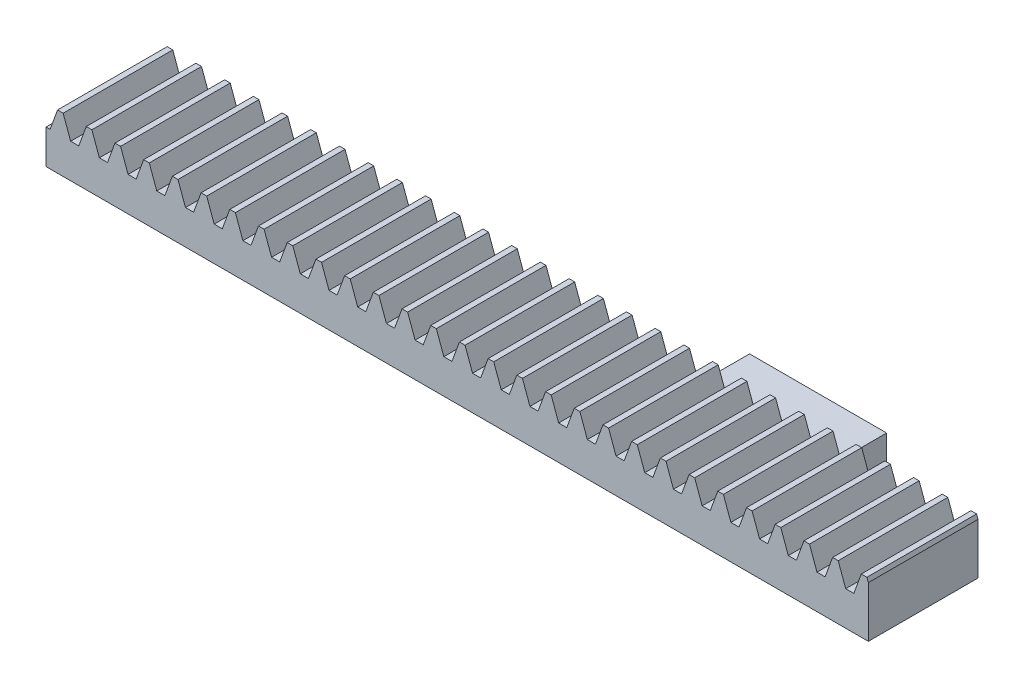
SolidWorks part; units mm, degrees
extrude "Blank" add sketch "BlankSke" against normal blind 12
sketch "BlankSke" plane through (0, 0, 0) normal (0, 0, 1) x (1, 0, 0)
  line L1 (0, 0) -> (90, 0)
  line L2 (0, 0) -> (0, 6)
  line L3 (0, 6) -> (90, 6)
  line L4 (90, 0) -> (90, 6)
  dimension "Length" = 90
ref_plane "Plane1" through (0, 0, 0) normal (0, 0, 1) x (1, 0, 0)
ref_plane "Plane2" through (0, 0, 0) normal (0, 1, 0) x (1, 0, 0)
ref_plane "Plane3" through (0, 0, 0) normal (1, 0, 0) x (0, 0, -1)
sketch "HoldingSke" plane through (0, 0, 0) normal (0, 1, 0) x (1, 0, 0)
  line L0 (0, 0) -> (0.1392, 0.9903)
  line L1 (-15, 0) -> (100, 0) construction
  line L2 (0, 0) -> (-2.1039, 2.3779)
  line L3 (0, 0) -> (-11.863, 4.5341)
  line L4 (0, 0) -> (7.479, 4.318)
  line L5 (0, 0) -> (-23.7986, -8.8762)
  line L6 (0, 0) -> (-10.5278, -7.1032)
  line L9 (-71.009, 38.7566) -> (13.5634, 69.5384)
  line L10 (-76.2, 3.3779) -> (-71.2, 3.3779)
  line L11 (0, 0) -> (-12, 0)
  line L12 (-76.2, 101.6) -> (-76.162, 101.6)
  line L13 (24.9733, 27.94) -> (52.9518, 28.4284)
  line L14 (24.9733, 27.94) -> (24.9743, 27.94)
  line L15 (24.9733, 27.94) -> (100.4006, 29.5858)
  circle A0 centre (0, 0) radius 19.05
  circle A1 centre (0, 0) radius 2.5
  circle A2 centre (0, 0) radius 12.7
  dimension "Num_teeth" = 30
  dimension "Width" = 12
  dimension "Length" = 90
  dimension "Pitch_height" = 5
sketch "TooCutSkeIll" plane through (0, 0, 0) normal (0, 0, 1) x (1, 0, 0)
  line L0 (-1.2538, 5.9737) -> (-0.5045, 3.9152)
  line L1 (-0.2687, 3.75) -> (0.2687, 3.75)
  line L2 (0.5045, 3.9152) -> (1.2538, 5.9737)
  line L3 (90, 6) -> (0, 6) construction
  line L4 (0, 0) -> (0, 64.897) construction
  line L5 (-13.208, 5) -> (12.954, 5) construction
  line L6 (0, 0) -> (90, 0) construction
  line L7 (0.8994, 5) -> (0.8994, 48.7463) construction
  line L8 (-0.8994, 5) -> (-0.8994, 48.7463) construction
  line L9 (1.2914, 6) -> (1.2914, 6.0254)
  line L10 (-1.2914, 6) -> (-1.2914, 6.0254)
  line L11 (-1.2914, 6.0254) -> (1.2914, 6.0254)
  arc A0 (0.2687, 3.75) -> (0.5045, 3.9152) centre (0.2687, 4.001) ccw
  arc A1 (-0.5045, 3.9152) -> (-0.2687, 3.75) centre (-0.2687, 4.001) ccw
  arc A2 (1.2914, 6) -> (1.2538, 5.9737) centre (1.2914, 5.96) ccw
  arc A3 (-1.2538, 5.9737) -> (-1.2914, 6) centre (-1.2914, 5.96) ccw
  dimension "Addendum_plus" = 1.0254
  dimension "Pitch_height" = 5
  dimension "Pressure_angle" = 20
  dimension "Gap_width" = 1.7988
  dimension "Dedendum" = 1.25
extrude "ToothCutIll" [suppressed] cut sketch "TooCutSkeIll" against normal through all
sketch "TooCutSkeSim" plane through (0, 0, 0) normal (0, 0, 1) x (1, 0, 0)
  line L0 (0.4444, 3.75) -> (-0.4444, 3.75)
  line L1 (1.2726, 6.0254) -> (0.4444, 3.75)
  line L2 (0, 17.4625) -> (0, 53.467) construction
  line L3 (1.2726, 6.0254) -> (-1.2726, 6.0254)
  line L6 (-1.2726, 6.0254) -> (-0.4444, 3.75)
  line L9 (-0.8994, 5) -> (0.8994, 5) construction
  line L10 (0, 0) -> (90, 0) construction
  line L11 (0.8994, 5) -> (0.8994, 53.467) construction
  line L12 (-0.8994, 5) -> (-0.8994, 53.467) construction
  dimension "Addendum_plus" = 1.0254
  dimension "Pitch_height" = 5
  dimension "Pressure_angle" = 20
  dimension "Gap_width" = 1.7988
  dimension "Dedendum" = 1.25
extrude "ToothCutSim" cut sketch "TooCutSkeSim" against normal through all
pattern_linear "TeethCuts" count 30 spacing 3.1416 along (1, 0, 0) of "ToothCutIll", "ToothCutSim"
sketch "Sketch1" plane through (0, 0, -12) normal (0, 0, -1) x (-1, 0, 0)
  line L0 (0, 0) -> (-90, 0) construction
  line L1 (-75, 0) -> (-60, 0)
  line L2 (-75, 0) -> (-75, 3.75)
  line L3 (-75, 3.75) -> (-60, 3.75)
  line L4 (-60, 0) -> (-60, 3.75)
  line L5 (0, 3.75) -> (0, 0) construction
  dimension "D1" = 60
  dimension "D2" = 15
extrude "Boss-Extrude1" add sketch "Sketch1" along normal blind 5
equation "' \"Module@HoldingSke\" = 6.35"
equation "' \"Num_teeth@HoldingSke\" = 12"
equation "' \"Ap@HoldingSke\" =  20"
equation "' \"Ap@HoldingSke\" = 20"
equation "' \"Width@HoldingSke\" = 0.25 * 25.4"
equation "' \"Show_teeth@HoldingSke\" = 500"
equation "' \"Backlash@HoldingSke\" = 0.009 * 25.4"
equation "' \"Addendum_fac@HoldingSke\" = 1.0"
equation "' \"Dedendum_fac@HoldingSke\" = 1.25"
equation "' \"Dedendum_add@HoldingSke\" = 0.00005 * 25.4"
equation "' \"Clearance_fac@HoldingSke\" = 0.25"
equation "' \"Pitch_height@HoldingSke\" = 1 * 25.4"
equation "' \"Length@HoldingSke\" = 4.71 * 25.4"
equation "\"Pitch@HoldingSke\" = 1 / \"Module@HoldingSke\""
equation "\"MPH@HoldingSke\" = \"Dedendum_fac@HoldingSke\" / \"Pitch@HoldingSke\" + 2 * \"Dedendum_add@HoldingSke\" + 0.002 * 25.4"
equation "\"MPH@HoldingSke\" = ((sgn( \"MPH@HoldingSke\" - \"Pitch_height@HoldingSke\")+1)*( \"MPH@HoldingSke\" - \"Pitch_height@HoldingSke\"))/2 + \"Pitch_height@HoldingSke\""
equation "\"Blank_height@BlankSke\" = \"Pitch_height@HoldingSke\" + \"Addendum_fac@HoldingSke\"  / \"Pitch@HoldingSke\" "
equation "\"Length@BlankSke\" =  \"Length@HoldingSke\""
equation "\"Face_width@Blank\" = \"Width@HoldingSke\""
equation "\"Pressure_angle@TooCutSkeIll\" = \"Ap@HoldingSke\""
equation "\"Addendum_plus@TooCutSkeIll\" =  \"Addendum_fac@HoldingSke\"  / \"Pitch@HoldingSke\" + 0.001 *25.4"
equation "\"Dedendum@TooCutSkeIll\" = \"Dedendum_fac@HoldingSke\"  / \"Pitch@HoldingSke\""
equation "\"Pitch_height@TooCutSkeIll\" =  \"MPH@HoldingSke\""
equation "\"Gap_width@TooCutSkeIll\" = 3.14159265 / 2 / \"Pitch@HoldingSke\" + 6 * \"Backlash@HoldingSke\""
equation "\"Pressure_angle@TooCutSkeSim\" = \"Ap@HoldingSke\""
equation "\"Addendum_plus@TooCutSkeSim\" =  \"Addendum_fac@HoldingSke\"  / \"Pitch@HoldingSke\" + 0.001 * 25.4"
equation "\"Dedendum@TooCutSkeSim\" = \"Dedendum_fac@HoldingSke\"  / \"Pitch@HoldingSke\""
equation "\"Pitch_height@TooCutSkeSim\" =  \"MPH@HoldingSke\""
equation "\"Gap_width@TooCutSkeSim\" = 3.14159265 / 2 / \"Pitch@HoldingSke\" + 6 * \"Backlash@HoldingSke\""
equation "\"Root_fillet@TooCutSkeIll\" = \"Clearance_fac@HoldingSke\" / \"Pitch@HoldingSke\" + \"Dedendum_add@HoldingSke\""
equation "\"Break_rad@TooCutSkeIll\" = 0.02 / \"Pitch@HoldingSke\" * 2"
equation "\"Linear_pitch@TeethCuts\" = 3.14159265 / \"Pitch@HoldingSke\""
equation "\"Num_teeth@HoldingSke\" = int( ( \"Length@HoldingSke\" + 0 ) / (3.14159265 / \"Pitch@HoldingSke\")) + 0.9999  + 1"
equation " \"Num_teeth@TeethCuts\" = int( \"Show_teeth@HoldingSke\" ) + 1"
equation " \"Num_teeth@TeethCuts\" = ((sgn( \"Num_teeth@TeethCuts\" - \"Num_teeth@HoldingSke\" )-1)*( \"Num_teeth@TeethCuts\" - \"Num_teeth@HoldingSke\" ))/-2+ \"Num_teeth@HoldingSke\""
equation " \"Num_teeth@TeethCuts\" = ((sgn( \"Num_teeth@TeethCuts\" - 2.0)+1)*( \"Num_teeth@TeethCuts\" - 2.0))/2 +2.0"
